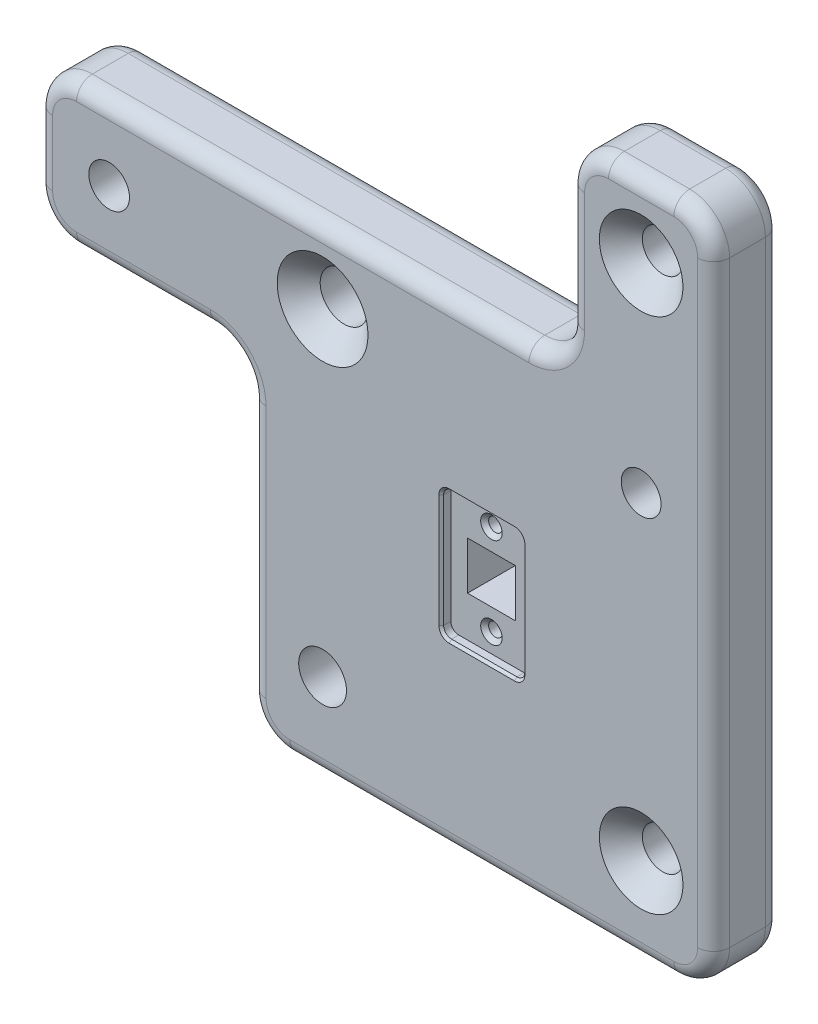
SolidWorks part; units mm, degrees
ref_plane "前视基准面" through (0, 0, 0) normal (0, 0, 1) x (1, 0, 0)
ref_plane "上视基准面" through (0, 0, 0) normal (0, 1, 0) x (1, 0, 0)
ref_plane "右视基准面" through (0, 0, 0) normal (1, 0, 0) x (0, 0, -1)
sketch "草图2" plane through (0, 0, 0) normal (0, 0, 1) x (1, 0, 0)
  line L1 (40, 0) -> (0, -40) construction
  line L2 (0, -40) -> (0, 0) construction
  line L3 (-10.9, 9.1) -> (25.9, 9.1)
  line L4 (-9.1, -14.1) -> (-9.1, -45.9)
  line L5 (-4.1, -50.9) -> (44.1, -50.9)
  line L6 (49.1, 9.1) -> (49.1, -45.9)
  line L7 (0, 0) -> (40, -40) construction
  line L8 (40, -40) -> (40, 0) construction
  line L9 (49.1, 9.1) -> (49.1, 29.1)
  line L10 (20, 17.2488) -> (20, -57.2488) construction
  line L11 (30.9, 14.1) -> (30.9, 29.1)
  line L12 (35.9, 34.1) -> (44.1, 34.1)
  line L13 (40, 0) -> (40, 34.6405) construction
  line L14 (-10.9, 9.1) -> (-30.9, 9.1)
  line L15 (-35.9, 4.1) -> (-35.9, -4.1)
  line L16 (-30.9, -9.1) -> (-14.1, -9.1)
  line L18 (17, -17) -> (23, -17)
  line L19 (17, -17) -> (17, -23)
  line L20 (17, -23) -> (23, -23)
  line L21 (23, -17) -> (23, -23)
  line L22 (17, -17) -> (23, -23) construction
  line L23 (17, -23) -> (23, -17) construction
  circle A0 centre (0, 0) radius 3
  circle A1 centre (40, 0) radius 2.5
  circle A2 centre (0, -40) radius 3
  circle A3 centre (40, -40) radius 2.55
  circle A4 centre (40, 25) radius 2.55
  circle A5 centre (-26.8, 0) radius 2.55
  arc A6 (49.1, 29.1) -> (44.1, 34.1) centre (44.1, 29.1) ccw
  arc A7 (30.9, 29.1) -> (35.9, 34.1) centre (35.9, 29.1) cw
  arc A8 (30.9, 14.1) -> (25.9, 9.1) centre (25.9, 14.1) cw
  arc A9 (44.1, -50.9) -> (49.1, -45.9) centre (44.1, -45.9) ccw
  arc A10 (-9.1, -45.9) -> (-4.1, -50.9) centre (-4.1, -45.9) ccw
  arc A11 (-14.1, -9.1) -> (-9.1, -14.1) centre (-14.1, -14.1) cw
  arc A12 (-35.9, -4.1) -> (-30.9, -9.1) centre (-30.9, -4.1) ccw
  arc A13 (-30.9, 9.1) -> (-35.9, 4.1) centre (-30.9, 4.1) ccw
  point P9 (20.9, -20.9)
  point P10 (20, -20)
  point P31 (49.1, 34.1)
  point P34 (30.9, 34.1)
  point P37 (30.9, 9.1)
  point P48 (-35.9, -9.1)
  point P51 (-35.9, 9.1)
  point P54 (20, -20)
  dimension "D1" = 6
  dimension "D2" = 5
  dimension "D4" = 6
  dimension "D6" = 5.1
  dimension "D17" = 5.1
  dimension "D18" = 5.1
  dimension "D19" = 5
  dimension "D3" = 40
  dimension "D5" = 40
  dimension "D7" = 6
  dimension "D8" = 60
  dimension "D9" = 25
  dimension "D10" = 9.1
  dimension "D11" = 9.1
  dimension "D12" = 9.1
  dimension "D13" = 25
  dimension "D14" = 18.2
  dimension "D15" = 18.2
  dimension "D16" = 9.1
  dimension "D20" = 6
  dimension "D24" = 40
  dimension "D25" = 9.1
  dimension "D26" = 9.1
extrude "凸台-拉伸2" add sketch "草图2" along normal blind 8.5
chamfer "倒角3" distance 2.7 angle 45 6 edges at (-24.25, 0, 0) (3, -40, 0) (42.5, 0, 0) (42.55, 25, 8.5) (3, 0, 8.5) (42.55, -40, 8.5)
sketch "草图3" plane through (0, 0, 8.5) normal (0, 0, 1) x (1, 0, 0)
  line L0 (0, 0) -> (40, -40) construction
  line L6 (40, 0) -> (0, -40) construction
  line L7 (15.9, -11.9) -> (24.1, -11.9)
  line L8 (14.9, -12.9) -> (14.9, -27.1)
  line L9 (15.9, -28.1) -> (24.1, -28.1)
  line L10 (25.1, -12.9) -> (25.1, -27.1)
  line L11 (14.9, -11.9) -> (25.1, -28.1) construction
  line L12 (14.9, -28.1) -> (25.1, -11.9) construction
  arc A0 (24.1, -28.1) -> (25.1, -27.1) centre (24.1, -27.1) ccw
  arc A1 (14.9, -27.1) -> (15.9, -28.1) centre (15.9, -27.1) ccw
  arc A2 (24.1, -11.9) -> (25.1, -12.9) centre (24.1, -12.9) cw
  arc A3 (15.9, -11.9) -> (14.9, -12.9) centre (15.9, -12.9) ccw
  point P4 (20, -20)
  dimension "D3" = 1
  dimension "D1" = 16.2
  dimension "D2" = 10.2
extrude "切除-拉伸1" cut sketch "草图3" against normal blind 1.2
sketch "草图4" plane through (0, 0, 7.3) normal (0, 0, 1) x (1, 0, 0)
  line L0 (14.9, -20) -> (25.1, -20) construction
  line L1 (14.9, -12.9) -> (14.9, -27.1) construction
  line L2 (25.1, -27.1) -> (25.1, -12.9) construction
  line L4 (24.1, -11.9) -> (15.9, -11.9) construction
  line L5 (20, -11.9) -> (20, -28.1) construction
  line L6 (15.9, -28.1) -> (24.1, -28.1) construction
  circle A0 centre (20, -14.3) radius 0.85
  circle A1 centre (20, -25.7) radius 0.85
  dimension "D2" = 1.7
  dimension "D1" = 5.7
extrude "切除-拉伸2" cut sketch "草图4" against normal blind 5
sketch "草图5" plane through (0, 0, 0) normal (0, 0, -1) x (-1, 0, 0)
  line L0 (-40, 0) -> (0, 0) construction
  line L1 (0, 0) -> (0, -40) construction
  line L2 (0, -40) -> (-40, -40) construction
  line L3 (-40, -40) -> (-40, 0) construction
  line L4 (-27.1, -14.9) -> (-12.9, -14.9)
  line L5 (-28.1, -15.9) -> (-28.1, -24.1)
  line L6 (-27.1, -25.1) -> (-12.9, -25.1)
  line L7 (-11.9, -15.9) -> (-11.9, -24.1)
  line L8 (-28.1, -14.9) -> (-11.9, -25.1) construction
  line L9 (-28.1, -25.1) -> (-11.9, -14.9) construction
  line L12 (-20, 0) -> (-20, -40) construction
  line L16 (-40, -20) -> (0, -20) construction
  arc A0 (-12.9, -14.9) -> (-11.9, -15.9) centre (-12.9, -15.9) cw
  arc A1 (-12.9, -25.1) -> (-11.9, -24.1) centre (-12.9, -24.1) ccw
  arc A2 (-28.1, -24.1) -> (-27.1, -25.1) centre (-27.1, -24.1) ccw
  arc A3 (-27.1, -14.9) -> (-28.1, -15.9) centre (-27.1, -15.9) ccw
  point P4 (-20, -20)
  dimension "D3" = 1
  dimension "D1" = 16.2
  dimension "D2" = 10.2
extrude "切除-拉伸3" cut sketch "草图5" against normal blind 1.2
sketch "草图6" plane through (0, 0, 1.2) normal (0, 0, -1) x (-1, 0, 0)
  line L0 (-20, -15.15) -> (-20, -24.85) construction
  line L1 (-28.1, -20) -> (-11.9, -20) construction
  line L2 (-28.1, -15.9) -> (-28.1, -24.1) construction
  line L3 (-11.9, -24.1) -> (-11.9, -15.9) construction
  arc A0 (-20.6021, -14.9) -> (-19.3979, -14.9) centre (-20, -14.3) ccw construction
  arc A1 (-19.3979, -25.1) -> (-20.6021, -25.1) centre (-20, -25.7) ccw construction
  circle A2 centre (-25.7, -20) radius 0.85
  circle A3 centre (-14.3, -20) radius 0.85
  dimension "D1" = 1.7
  dimension "D2" = 5.7
extrude "切除-拉伸4" cut sketch "草图6" against normal blind 5
fillet "圆角2" radius 2 32 edges at (-34.4355, 7.6355, 0) (-2.5, 9.1, 0) (29.4355, 10.5645, 0) (30.9, 21.6, 0) (32.3645, 32.6355, 0) (40, 34.1, 0) (47.6355, 32.6355, 0) (49.1, -8.4, 0) (47.6355, -49.4355, 0) (20, -50.9, 0) (-7.6355, -49.4355, 0) (-9.1, -30, 0) (-10.5645, -10.5645, 0) (-22.5, -9.1, 0) (-34.4355, -7.6355, 0) (29.4355, 10.5645, 8.5) (30.9, 21.6, 8.5) (32.3645, 32.6355, 8.5) (40, 34.1, 8.5) (47.6355, 32.6355, 8.5) (49.1, -8.4, 8.5) (47.6355, -49.4355, 8.5) (20, -50.9, 8.5) (-7.6355, -49.4355, 8.5) (-9.1, -30, 8.5) (-10.5645, -10.5645, 8.5) (-22.5, -9.1, 8.5) (-34.4355, -7.6355, 8.5) (-35.9, 0, 8.5) (-34.4355, 7.6355, 8.5) (-35.9, 0, 0) (-2.5, 9.1, 8.5)
sketch "草图7" plane through (0, 0, 0) normal (0, 0, -1) x (-1, 0, 0)
  line L1 (-27, -30.1) -> (-13, -30.1)
  line L2 (-28, -31.1) -> (-28, -43.1)
  line L3 (-27, -44.1) -> (-23.1, -44.1)
  line L4 (-12, -31.1) -> (-12, -43.1)
  line L5 (-28, -30.1) -> (-12, -44.1) construction
  line L6 (-28, -44.1) -> (-12, -30.1) construction
  line L8 (-27.1, -25.1) -> (-12.9, -25.1) construction
  line L9 (-20, -48.9) -> (-20, -25.1) construction
  line L10 (-44.1, -48.9) -> (4.1, -48.9) construction
  line L11 (-27.1, -25.1) -> (-12.9, -25.1) construction
  line L12 (-28, -37.1) -> (-12, -37.1) construction
  line L13 (-16.9, -44.1) -> (-13, -44.1)
  line L15 (-23.1, -44.1) -> (-23.1, -47.6276)
  line L16 (-23.1, -47.6276) -> (-16.9, -47.6276)
  line L17 (-16.9, -44.1) -> (-16.9, -47.6276)
  arc A0 (-13, -30.1) -> (-12, -31.1) centre (-13, -31.1) cw
  arc A1 (-27, -30.1) -> (-28, -31.1) centre (-27, -31.1) ccw
  arc A2 (-13, -44.1) -> (-12, -43.1) centre (-13, -43.1) ccw
  arc A3 (-28, -43.1) -> (-27, -44.1) centre (-27, -43.1) ccw
  point P0 (-20, -37.1)
  point P19 (-20, -44.1)
  dimension "D3" = 1
  dimension "D1" = 14
  dimension "D2" = 16
  dimension "D4" = 5
  dimension "D5" = 6.2
chamfer "倒角5" distance 0.3 angle 45 16 edges at (11.9, -20, 0) (12.1929, -15.1929, 0) (12.1929, -24.8071, 0) (20, -14.9, 0) (20, -25.1, 0) (27.8071, -15.1929, 0) (27.8071, -24.8071, 0) (28.1, -20, 0) (14.9, -20, 8.5) (15.1929, -27.8071, 8.5) (15.1929, -12.1929, 8.5) (20, -28.1, 8.5) (20, -11.9, 8.5) (24.8071, -27.8071, 8.5) (24.8071, -12.1929, 8.5) (25.1, -20, 8.5)
chamfer "倒角6" distance 0.5 angle 45 4 edges at (19.15, -25.7, 7.3) (20.85, -14.3, 7.3) (24.85, -20, 1.2) (15.15, -20, 1.2)
extrude "切除-拉伸11" cut sketch "草图7" against normal blind 2.5
sketch "草图14" plane through (0, 0, 2.5) normal (0, 0, -1) x (-1, 0, 0)
  line L0 (-16.9, -47.6276) -> (-16.9, -44.1) construction
  line L5 (-23.1, -47.6276) -> (-16.9, -47.6276)
  line L6 (-23.1, -47.6276) -> (-23.1, -32.6276)
  line L7 (-23.1, -32.6276) -> (-16.9, -32.6276)
  line L8 (-16.9, -47.6276) -> (-16.9, -32.6276)
  dimension "D1" = 0
  dimension "D2" = 15
extrude "切除-拉伸12" cut sketch "草图14" against normal blind 0.6
fillet "圆角7" radius 4 1 edges at (20, -47.6276, 3.1)
sketch "草图15" plane through (0, 0, 2.5) normal (0, 0, -1) x (-1, 0, 0)
  line L0 (-28, -37.1) -> (-12, -37.1) construction
  line L1 (-28, -31.1) -> (-28, -43.1) construction
  line L2 (-12, -43.1) -> (-12, -31.1) construction
  line L4 (-13, -30.1) -> (-27, -30.1) construction
  line L5 (-20, -30.1) -> (-20, -47.6276) construction
  line L6 (-23.1, -47.6276) -> (-16.9, -47.6276) construction
  circle A0 centre (-25, -33.1) radius 0.85
  circle A1 centre (-15, -33.1) radius 0.85
  circle A2 centre (-15, -41.1) radius 0.85
  circle A3 centre (-25, -41.1) radius 0.85
  dimension "D1" = 1.7
  dimension "D2" = 5
  dimension "D3" = 4
extrude "切除-拉伸13" cut sketch "草图15" against normal blind 5
fillet "圆角8" radius 8 1 edges at (20, -47.6276, 0)
chamfer "倒角7" distance 0.2 angle 45 9 edges at (14.95, -44.1, 0) (25.05, -44.1, 0) (12.2929, -43.8071, 0) (27.7071, -43.8071, 0) (12, -37.1, 0) (28, -37.1, 0) (12.2929, -30.3929, 0) (27.7071, -30.3929, 0) (20, -30.1, 0)
